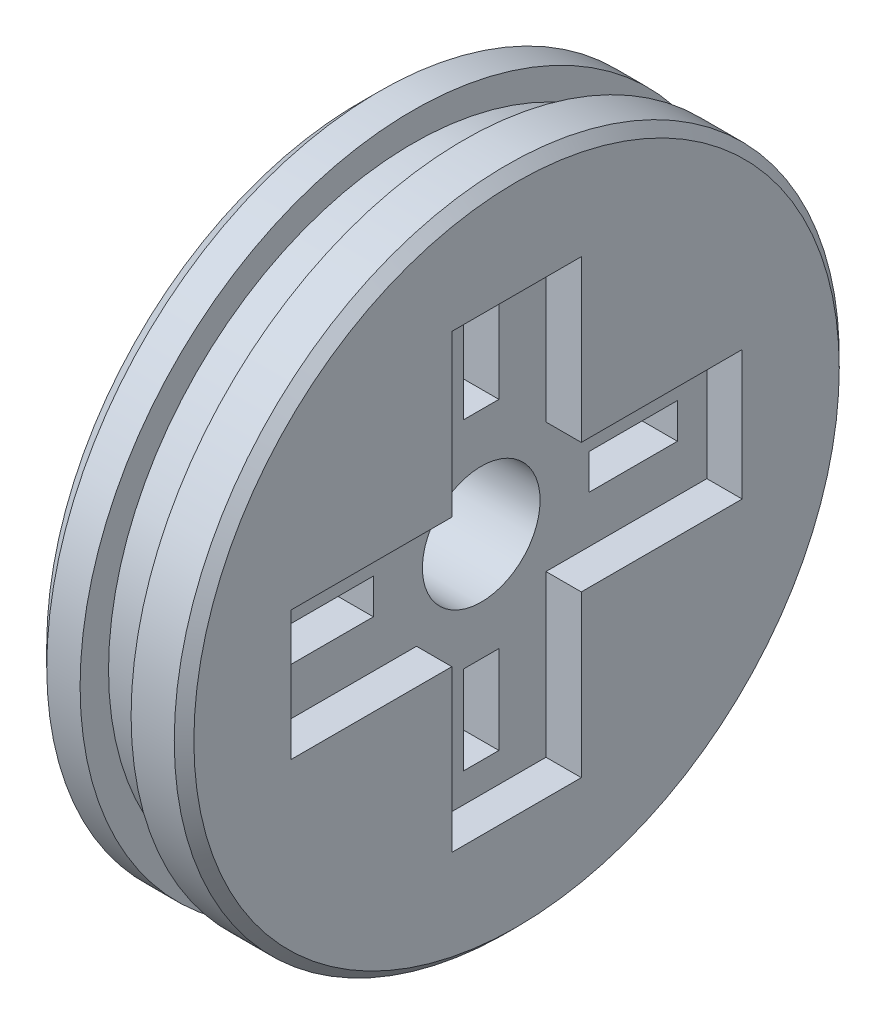
SolidWorks part; units mm, degrees
ref_plane "Front Plane" through (0, 0, 0) normal (0, 0, 1) x (1, 0, 0)
ref_plane "Top Plane" through (0, 0, 0) normal (0, 1, 0) x (1, 0, 0)
ref_plane "Right Plane" through (0, 0, 0) normal (1, 0, 0) x (0, 0, -1)
ref_plane "Plane1" through (0, 0, -52) normal (0, 0, 1) x (1, 0, 0)
sketch "Sketch1" plane through (0, 0, -52) normal (0, 0, 1) x (1, 0, 0)
  line L0 (-90.2, -65) -> (-72.2, -65) construction
  line L1 (-77.2, -65) -> (-85.2, -65)
  line L2 (-85.2, -65) -> (-85.2, -49.05)
  line L3 (-85.2, -49.05) -> (-84.2, -48.05)
  line L4 (-84.2, -48.05) -> (-77.7, -48.05)
  line L5 (-77.7, -48.05) -> (-77.2, -48.55)
  line L6 (-77.2, -48.55) -> (-77.2, -65)
revolve "Revolve1" add sketch "Sketch1" angle 360 about L0
sketch "Sketch2" plane through (0, 0, -52) normal (0, 0, 1) x (1, 0, 0)
  line L0 (-87.5, -65) -> (-74.9, -65) construction
  line L1 (-79.9, -49.5) -> (-82.5, -49.5)
  line L2 (-82.5, -49.5) -> (-82.5, -47.05)
  line L3 (-82.5, -47.05) -> (-79.9, -47.05)
  line L4 (-79.9, -47.05) -> (-79.9, -49.5)
revolve "Revolve2" add sketch "Sketch2" angle 360 about L0
combine bodies "Combine1" operation type subtract main body 101 bodies to subtract 102
sketch "Sketch3" plane through (0, 0, 0) normal (0, 0, 1) x (1, 0, 0)
  line L1 (-79, -76.5) -> (-76.7, -76.5)
  line L2 (-79, -76.5) -> (-79, -53.5)
  line L3 (-79, -53.5) -> (-76.7, -53.5)
  line L4 (-76.7, -76.5) -> (-76.7, -53.5)
extrude "Boss-Extrude1" add sketch "Sketch3" along normal blind 6.6 from offset 55.3 separate body offset against normal yes
combine bodies "Combine2" operation type subtract main body 103 bodies to subtract 104
sketch "Sketch4" plane through (0, 0, 0) normal (0, 0, 1) x (1, 0, 0)
  line L1 (-79, -68.3) -> (-76.7, -68.3)
  line L2 (-79, -68.3) -> (-79, -61.7)
  line L3 (-79, -61.7) -> (-76.7, -61.7)
  line L4 (-76.7, -68.3) -> (-76.7, -61.7)
extrude "Boss-Extrude2" add sketch "Sketch4" along normal blind 23 from offset 63.5 separate body offset against normal yes
combine bodies "Combine3" operation type subtract main body 105 bodies to subtract 106
sketch "Sketch5" plane through (0, 0, 0) normal (1, 0, 0) x (0, 0, -1)
  circle A0 centre (52, -65) radius 4.6
extrude "Boss-Extrude3" add sketch "Sketch5" along normal blind 2.3 from offset 79 separate body offset against normal yes
combine bodies "Combine4" operation type subtract main body 107 bodies to subtract 108
sketch "Sketch6" plane through (0, 0, 0) normal (1, 0, 0) x (0, 0, -1)
  circle A0 centre (52, -65) radius 7.1
extrude "Boss-Extrude4" add sketch "Sketch6" along normal blind 1.7 from offset 85.7 separate body offset against normal yes
combine bodies "Combine5" operation type subtract main body 109 bodies to subtract 110
sketch "Sketch7" plane through (0, 0, 0) normal (1, 0, 0) x (0, 0, -1)
  circle A0 centre (52, -65) radius 3
extrude "Boss-Extrude5" add sketch "Sketch7" along normal blind 5.2 from offset 84.1 separate body offset against normal yes
combine bodies "Combine6" operation type subtract main body 111 bodies to subtract 112
sketch "Sketch8" plane through (0, 0, 0) normal (0, 0, 1) x (1, 0, 0)
  line L1 (-83, -59.5) -> (-78.9, -59.5)
  line L2 (-83, -59.5) -> (-83, -57.4)
  line L3 (-83, -57.4) -> (-78.9, -57.4)
  line L4 (-78.9, -59.5) -> (-78.9, -57.4)
extrude "Boss-Extrude6" add sketch "Sketch8" along normal blind 1.8 from offset 52.9 separate body offset against normal yes
combine bodies "Combine7" operation type subtract main body 113 bodies to subtract 114
sketch "Sketch9" plane through (0, 0, 0) normal (0, 0, 1) x (1, 0, 0)
  line L1 (-83, -65.9) -> (-78.9, -65.9)
  line L2 (-83, -65.9) -> (-83, -64.1)
  line L3 (-83, -64.1) -> (-78.9, -64.1)
  line L4 (-78.9, -65.9) -> (-78.9, -64.1)
extrude "Boss-Extrude7" add sketch "Sketch9" along normal blind 2.1 from offset 46.5 separate body offset against normal yes
combine bodies "Combine8" operation type subtract main body 115 bodies to subtract 116
sketch "Sketch10" plane through (0, 0, 0) normal (0, 0, 1) x (1, 0, 0)
  line L1 (-83, -72.6) -> (-78.9, -72.6)
  line L2 (-83, -72.6) -> (-83, -70.5)
  line L3 (-83, -70.5) -> (-78.9, -70.5)
  line L4 (-78.9, -72.6) -> (-78.9, -70.5)
extrude "Boss-Extrude8" add sketch "Sketch10" along normal blind 1.8 from offset 52.9 separate body offset against normal yes
combine bodies "Combine9" operation type subtract main body 117 bodies to subtract 118
sketch "Sketch11" plane through (0, 0, 0) normal (0, 0, 1) x (1, 0, 0)
  line L1 (-83, -65.9) -> (-78.9, -65.9)
  line L2 (-83, -65.9) -> (-83, -64.1)
  line L3 (-83, -64.1) -> (-78.9, -64.1)
  line L4 (-78.9, -65.9) -> (-78.9, -64.1)
extrude "Boss-Extrude9" add sketch "Sketch11" along normal blind 2.1 from offset 59.6 separate body offset against normal yes
combine bodies "Combine10" operation type subtract main body 119 bodies to subtract 120
sketch "Sketch12" plane through (0, 0, 0) normal (0, 0, 1) x (1, 0, 0)
  line L1 (-84.2, -57.4) -> (-78.9, -57.4)
  line L2 (-84.2, -57.4) -> (-84.2, -55)
  line L3 (-84.2, -55) -> (-78.9, -55)
  line L4 (-78.9, -57.4) -> (-78.9, -55)
extrude "Boss-Extrude10" add sketch "Sketch12" along normal blind 1.8 from offset 52.9 separate body offset against normal yes
combine bodies "Combine11" operation type subtract main body 121 bodies to subtract 122
sketch "Sketch13" plane through (0, 0, 0) normal (0, 0, 1) x (1, 0, 0)
  line L1 (-84.2, -65.9) -> (-78.9, -65.9)
  line L2 (-84.2, -65.9) -> (-84.2, -64.1)
  line L3 (-84.2, -64.1) -> (-78.9, -64.1)
  line L4 (-78.9, -65.9) -> (-78.9, -64.1)
extrude "Boss-Extrude11" add sketch "Sketch13" along normal blind 2.4 from offset 44.4 separate body offset against normal yes
combine bodies "Combine12" operation type subtract main body 123 bodies to subtract 124
sketch "Sketch14" plane through (0, 0, 0) normal (0, 0, 1) x (1, 0, 0)
  line L1 (-84.2, -75) -> (-78.9, -75)
  line L2 (-84.2, -75) -> (-84.2, -72.6)
  line L3 (-84.2, -72.6) -> (-78.9, -72.6)
  line L4 (-78.9, -75) -> (-78.9, -72.6)
extrude "Boss-Extrude12" add sketch "Sketch14" along normal blind 1.8 from offset 52.9 separate body offset against normal yes
combine bodies "Combine13" operation type subtract main body 125 bodies to subtract 126
sketch "Sketch15" plane through (0, 0, 0) normal (0, 0, 1) x (1, 0, 0)
  line L1 (-84.2, -65.9) -> (-78.9, -65.9)
  line L2 (-84.2, -65.9) -> (-84.2, -64.1)
  line L3 (-84.2, -64.1) -> (-78.9, -64.1)
  line L4 (-78.9, -65.9) -> (-78.9, -64.1)
extrude "Boss-Extrude13" add sketch "Sketch15" along normal blind 2.4 from offset 62 separate body offset against normal yes
combine bodies "Combine14" operation type subtract main body 127 bodies to subtract 128
